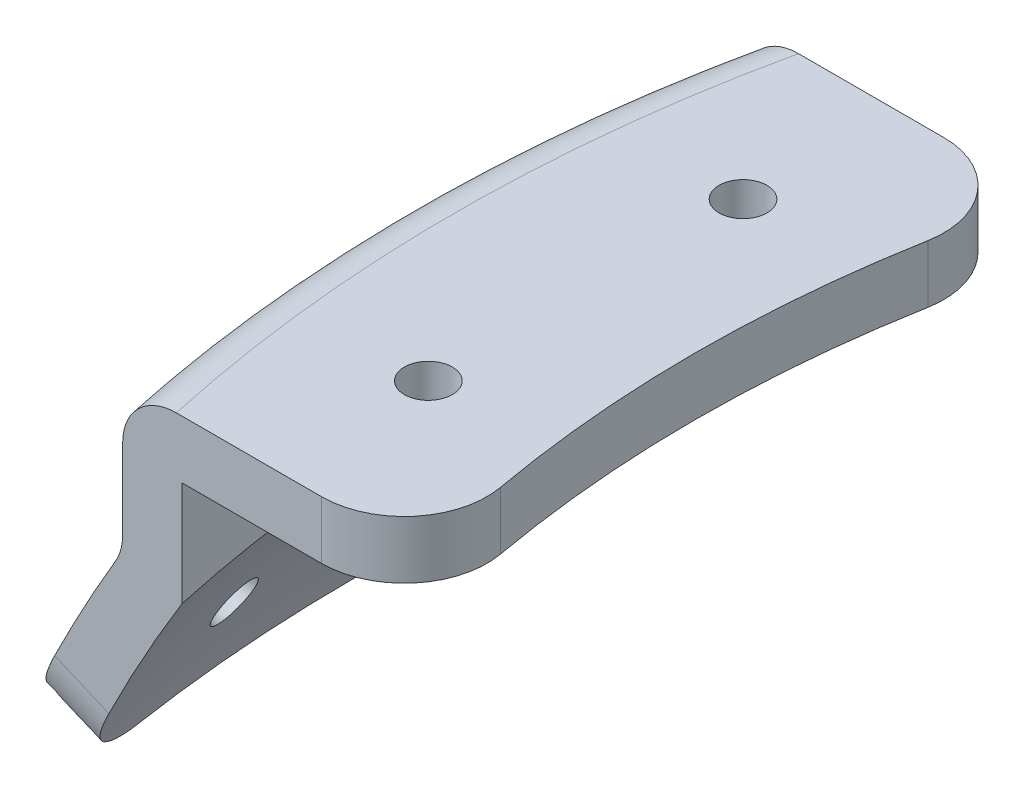
SolidWorks part; units mm, degrees
material "Polyether Polyol"
ref_plane "Front Plane" through (0, 0, 0) normal (0, 0, 1) x (1, 0, 0)
ref_plane "Top Plane" through (0, 0, 0) normal (0, 1, 0) x (1, 0, 0)
ref_plane "Right Plane" through (0, 0, 0) normal (1, 0, 0) x (0, 0, -1)
sketch "Sketch2" plane through (0, 0, 0) normal (0, 0, 1) x (1, 0, 0)
  line L0 (-193.0406, 173.0706) -> (-186.612, 170.3005) construction
  line L1 (-181.1012, 214.3685) -> (-181.1012, 196.5948) construction
  line L2 (-174.1012, 207.3685) -> (-174.1012, 194.6685) construction
  line L3 (-145.5262, 207.3685) -> (-174.1012, 207.3685) construction
  line L4 (-145.5262, 207.3685) -> (-145.5262, 214.3685) construction
  line L5 (-145.5262, 214.3685) -> (-181.1012, 214.3685) construction
  line L6 (-193.0406, 173.0706) -> (-186.612, 170.3005)
  line L7 (-181.1012, 214.3685) -> (-181.1012, 196.5948)
  line L8 (-174.1012, 207.3685) -> (-174.1012, 194.6685)
  line L9 (-145.5262, 207.3685) -> (-174.1012, 207.3685)
  line L10 (-145.5262, 207.3685) -> (-145.5262, 214.3685)
  line L11 (-145.5262, 214.3685) -> (-181.1012, 214.3685)
  line L12 (0, 0) -> (0, 215.8974) construction
  arc A0 (-181.1012, 196.5948) -> (-193.0406, 173.0706) centre (0, 89.8878) ccw construction
  arc A1 (-174.1012, 194.6685) -> (-186.612, 170.3005) centre (0, 89.8878) ccw construction
  arc A2 (-181.1012, 196.5948) -> (-193.0406, 173.0706) centre (0, 89.8878) ccw
  arc A3 (-174.1012, 194.6685) -> (-186.612, 170.3005) centre (0, 89.8878) ccw
revolve "Revolve1" add sketch "Sketch2" angle 30 mid plane about L12
fillet "Fillet1" radius 6.35 2 edges at (-181.1012, 196.5948, 0) (-181.1012, 214.3685, 0)
sketch "Sketch3" plane through (0, 207.3685, 0) normal (0, -1, 0) x (1, 0, 0)
  circle A0 centre (-158.75, 19.05) radius 3.5719 construction
  circle A1 centre (-158.75, -19.05) radius 3.5719 construction
  circle A2 centre (-158.75, 19.05) radius 3.5719 construction
  circle A3 centre (-158.75, -19.05) radius 3.5719 construction
  circle A4 centre (-158.75, -19.05) radius 2.9
  circle A5 centre (-158.75, 19.05) radius 2.9
  dimension "D1" = 5.8
extrude "Cut-Extrude1" cut sketch "Sketch3" against normal through all both and the other way through all
sketch "Sketch4" plane through (0, 214.3685, 0) normal (0, 1, 0) x (1, 0, 0)
  line L1 (-140.5675, 37.665) -> (-215.4275, 37.665)
  line L2 (-140.5675, 37.665) -> (-140.5675, -37.665)
  line L3 (-140.5675, -37.665) -> (-215.4275, -37.665)
  line L4 (-215.4275, 37.665) -> (-215.4275, -37.665)
extrude "Cut-Extrude2" cut sketch "Sketch4" against normal through all flip side to cut
fillet "Fillet2" radius 10 4 edges at (-140.5675, 210.8685, -37.665) (-140.5675, 210.8685, 37.665)
sketch "Sketch5" plane through (0, 0, 0) normal (0, 0, 1) x (1, 0, 0)
  line L0 (0, 89.8878) -> (-181.0525, 182.1386) construction
  line L1 (0, 0) -> (0, 215.8974) construction
  arc A1 (-174.1012, 194.6685) -> (-186.612, 170.3005) centre (0, 89.8878) ccw construction
  dimension "D1" = 63
ref_plane "Plane1" through (36.3604, 71.3612, 0) normal (0.454, 0.891, 0) x (-0.891, 0.454, 0)
sketch "Sketch6" plane through (36.3604, 71.3612, 0) normal (0.454, 0.891, 0) x (-0.891, 0.454, 0)
  line L0 (216.8377, 18.9708) -> (270.6406, 23.678) construction
  line L1 (40.8082, 0) -> (244.0082, 0) construction
  line L2 (216.8377, 18.9708) -> (271.2422, 23.7306)
  line L3 (216.8377, 18.9708) -> (216.5849, 21.8598)
  line L4 (271.2422, 23.7306) -> (270.9894, 26.6196)
  line L5 (216.5849, 21.8598) -> (270.9894, 26.6196)
  dimension "D1" = 5
  dimension "D2" = 2.9
revolve "Cut-Revolve1" cut sketch "Sketch6" angle 360 about L0
mirror "Mirror1" about plane through (0, 0, 0) normal (0, 0, 1) of "Cut-Revolve1"
